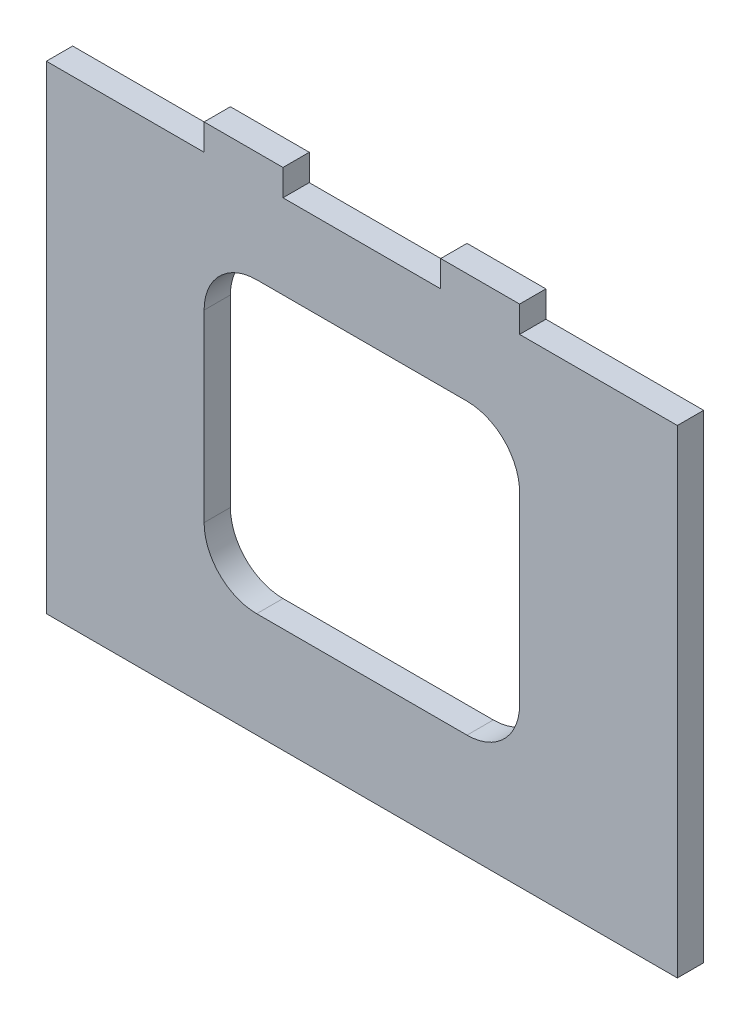
SolidWorks part; units mm, degrees
ref_plane "Ebene vorne" through (0, 0, 0) normal (0, 0, 1) x (1, 0, 0)
ref_plane "Ebene oben" through (0, 0, 0) normal (0, 1, 0) x (1, 0, 0)
ref_plane "Ebene rechts" through (0, 0, 0) normal (1, 0, 0) x (0, 0, -1)
sketch "Skizze1" plane through (0, 0, 0) normal (0, 0, 1) x (1, 0, 0)
  line L1 (0, 0) -> (120, 0)
  line L2 (0, 0) -> (0, 91)
  line L3 (0, 91) -> (120, 91)
  line L4 (120, 0) -> (120, 91)
  dimension "D1" = 120
  dimension "D2" = 91
extrude "Grundplatte" add sketch "Skizze1" along normal blind 5
sketch "Skizze2" plane through (0, 0, 5) normal (0, 0, 1) x (1, 0, 0)
  line L0 (60, 91) -> (60, 75) construction
  line L1 (30, 75) -> (90, 75)
  line L2 (30, 75) -> (30, 20)
  line L3 (30, 20) -> (90, 20)
  line L4 (90, 75) -> (90, 20)
  line L5 (120, 91) -> (0, 91) construction
  line L6 (60, 75) -> (60, 20) construction
  line L7 (60, 20) -> (60, 0) construction
  line L8 (0, 0) -> (120, 0) construction
  dimension "D1" = 55
  dimension "D2" = 60
  dimension "D3" = 20
extrude "Durchbruch" cut sketch "Skizze2" against normal through all
fillet "Verrundung1" radius 10 4 edges at (30, 20, 2.5) (90, 20, 2.5) (90, 75, 2.5) (30, 75, 2.5)
sketch "Skizze3" plane through (0, 91, 0) normal (0, 1, 0) x (1, 0, 0)
  line L0 (60, 0) -> (60, -5) construction
  line L5 (120, 0) -> (0, 0) construction
  line L6 (120, -5) -> (0, -5) construction
  line L7 (75, 0) -> (75, -5)
  line L8 (30, 0) -> (45, 0)
  line L9 (30, 0) -> (30, -5)
  line L10 (30, -5) -> (45, -5)
  line L11 (45, 0) -> (45, -5)
  line L12 (90, -5) -> (75, -5)
  line L13 (90, 0) -> (90, -5)
  line L14 (90, 0) -> (75, 0)
  dimension "D1" = 15
  dimension "D2" = 30
extrude "Zapfen" add sketch "Skizze3" along normal blind 5
